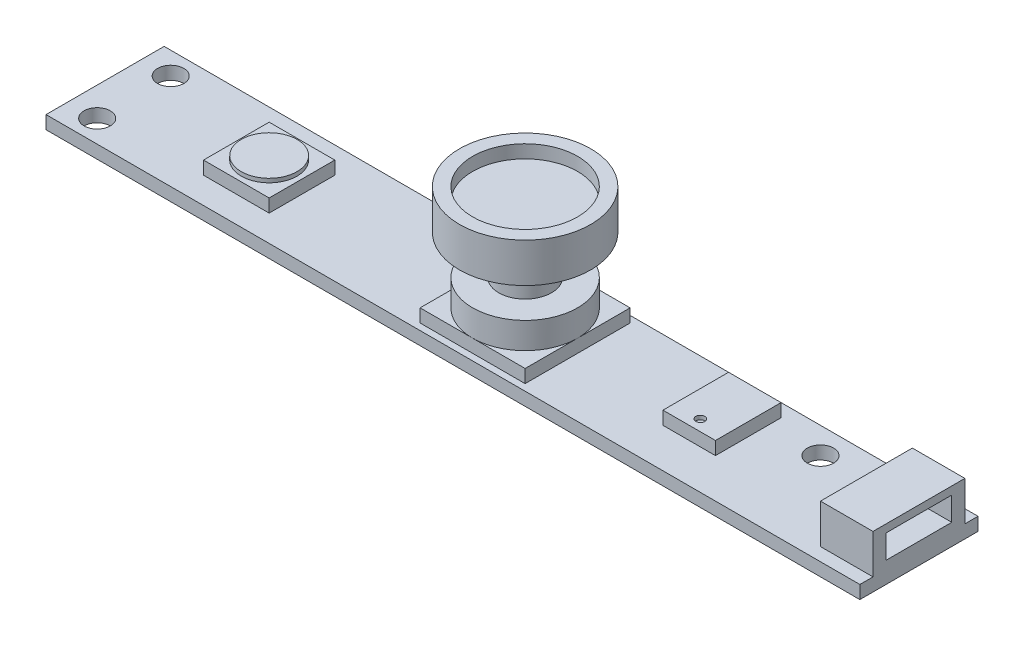
SolidWorks part; units mm, degrees
ref_plane "Front Plane" through (0, 0, 0) normal (0, 0, 1) x (1, 0, 0)
ref_plane "Top Plane" through (0, 0, 0) normal (0, 1, 0) x (1, 0, 0)
ref_plane "Right Plane" through (0, 0, 0) normal (1, 0, 0) x (0, 0, -1)
sketch "Sketch1" plane through (0, 0, 0) normal (0, 1, 0) x (1, 0, 0)
  line L1 (0, 0) -> (62, 0)
  line L2 (0, 0) -> (0, 9)
  line L3 (0, 9) -> (62, 9)
  line L4 (62, 0) -> (62, 9)
  dimension "D1" = 9
  dimension "D2" = 62
extrude "Boss-Extrude1" add sketch "Sketch1" along normal blind 1
sketch "Sketch2" plane through (0, 1, 0) normal (0, 1, 0) x (1, 0, 0)
  line L0 (62, 4.5) -> (0, 4.5) construction
  line L1 (62, 0) -> (62, 9) construction
  line L2 (0, 9) -> (0, 0) construction
  line L3 (31, 9) -> (31, 0) construction
  line L4 (62, 9) -> (0, 9) construction
  line L5 (0, 0) -> (62, 0) construction
  line L6 (62, 4.5) -> (62, 8)
  line L7 (62, 4.5) -> (62, 1)
  line L8 (62, 8) -> (58, 8)
  line L9 (58, 8) -> (58, 1)
  line L10 (58, 1) -> (62, 1)
  dimension "D1" = 3.5
  dimension "D2" = 3.5
  dimension "D3" = 4
extrude "Boss-Extrude2" add sketch "Sketch2" along normal blind 3
sketch "Sketch3" plane through (62, 0, 0) normal (1, 0, 0) x (0, 0, -1)
  line L11 (2, 3.4) -> (7, 3.4)
  line L12 (2, 3.4) -> (2, 1.6)
  line L13 (2, 1.6) -> (7, 1.6)
  line L14 (7, 3.4) -> (7, 1.6)
extrude "Cut-Extrude1" cut sketch "Sketch3" against normal blind 3
sketch "Sketch4" plane through (0, 1, 0) normal (0, 1, 0) x (1, 0, 0)
  line L0 (0, 4.5) -> (62, 4.5) construction
  line L1 (0, 9) -> (0, 0) construction
  line L2 (62, 1) -> (62, 8) construction
  line L4 (62, 9) -> (0, 9) construction
  line L5 (2.2, 9) -> (2.2, 0) construction
  line L6 (0, 0) -> (62, 0) construction
  circle A0 centre (2.2, 7.3) radius 1
  circle A1 centre (2.2, 1.7) radius 1
  circle A2 centre (52, 7) radius 1
extrude "Cut-Extrude2" cut sketch "Sketch4" against normal through all
sketch "Sketch5" plane through (0, 1, 0) normal (0, 1, 0) x (1, 0, 0)
  line L0 (62, 9) -> (62, 8)
  line L1 (62, 1) -> (62, 8) construction
  line L2 (62, 8) -> (31.4894, 8) construction
  line L3 (62, 9) -> (48, 9)
  line L4 (62, 9) -> (0, 9) construction
  line L5 (48, 9) -> (48, 0) construction
  line L6 (0, 0) -> (62, 0) construction
  line L8 (44, 9) -> (44, 0) construction
  line L9 (48, 8) -> (44, 8)
  line L10 (62, 3) -> (38.3098, 3) construction
  line L11 (48, 8) -> (48, 3)
  line L12 (48, 3) -> (44, 3)
  line L13 (44, 8) -> (44, 3)
  dimension "D1" = 1
  dimension "D2" = 14
extrude "Boss-Extrude4" add sketch "Sketch5" along normal blind 1 contours L9 L13 L12 L11 region at (46, 1, -5.5)
sketch "Sketch6" plane through (0, 1, 0) normal (0, 1, 0) x (1, 0, 0)
  line L0 (0, 9) -> (10, 9)
  line L1 (62, 9) -> (0, 9) construction
  line L2 (10, 9) -> (10, 0) construction
  line L3 (0, 0) -> (62, 0) construction
  line L4 (0, 4.5) -> (24.0117, 4.5) construction
  line L5 (0, 9) -> (0, 0) construction
  line L6 (10, 4.5) -> (10, 7)
  line L7 (10, 7) -> (15, 7)
  line L8 (15, 7) -> (15, 4.5)
  line L9 (15, 4.5) -> (15, 2)
  line L10 (15, 2) -> (10, 2)
  line L11 (10, 2) -> (10, 4.5)
  dimension "D1" = 10
  dimension "D2" = 2.5
  dimension "D3" = 2.5
  dimension "D4" = 5
extrude "Boss-Extrude5" add sketch "Sketch6" along normal blind 1 contours L11 L10 L9 L8 L7 L6 region at (12.5, 1, -4.5)
sketch "Sketch7" plane through (0, 2, 0) normal (0, 1, 0) x (1, 0, 0)
  line L0 (12.5, 7) -> (12.5, 2) construction
  line L1 (10, 7) -> (15, 7) construction
  line L2 (15, 2) -> (10, 2) construction
  line L3 (10, 4.5) -> (15, 4.5) construction
  line L4 (10, 2) -> (10, 7) construction
  line L5 (15, 7) -> (15, 2) construction
  circle A0 centre (12.5, 4.5) radius 2.126
extrude "Boss-Extrude6" add sketch "Sketch7" along normal blind 0.3
sketch "Sketch8" plane through (0, 1, 0) normal (0, 1, 0) x (1, 0, 0)
  line L0 (0, 4.5) -> (62, 4.5) construction
  line L1 (0, 9) -> (0, 0) construction
  line L2 (62, 1) -> (62, 8) construction
  line L3 (62, 9) -> (36, 9)
  line L4 (62, 9) -> (0, 9) construction
  line L5 (36, 9) -> (36, 0) construction
  line L6 (0, 0) -> (62, 0) construction
  line L7 (36, 9) -> (28, 9)
  line L8 (28, 9) -> (28, 0) construction
  line L9 (28, 4.5) -> (28, 0.5)
  line L10 (28, 0.5) -> (36, 0.5)
  line L11 (36, 0.5) -> (36, 4.5)
  line L12 (36, 4.5) -> (36, 8.5)
  line L13 (36, 8.5) -> (28, 8.5)
  line L14 (28, 8.5) -> (28, 4.5)
  dimension "D1" = 26
  dimension "D2" = 8
  dimension "D3" = 4
  dimension "D4" = 4
extrude "Boss-Extrude7" add sketch "Sketch8" along normal blind 1 contours L13 L14 L9 L10 L11 L12 region at (32, 1, -4.5)
sketch "Sketch9" plane through (0, 2, 0) normal (0, 1, 0) x (1, 0, 0)
  line L0 (28, 4.5) -> (36, 4.5) construction
  line L1 (28, 8.5) -> (28, 0.5) construction
  line L2 (36, 0.5) -> (36, 8.5) construction
  line L3 (32, 8.5) -> (32, 0.5) construction
  line L4 (36, 8.5) -> (28, 8.5) construction
  line L5 (28, 0.5) -> (36, 0.5) construction
  circle A0 centre (32, 4.5) radius 4
extrude "Boss-Extrude8" add sketch "Sketch9" along normal blind 2
sketch "Sketch10" plane through (0, 4, 0) normal (0, 1, 0) x (1, 0, 0)
  line L0 (32, 8.5) -> (32, 0.5) construction
  line L1 (28, 4.5) -> (36, 4.5) construction
  circle A0 centre (32, 4.5) radius 4 construction
  circle A1 centre (32, 4.5) radius 2.0145
extrude "Boss-Extrude9" add sketch "Sketch10" along normal blind 3
sketch "Sketch11" plane through (0, 7, 0) normal (0, 1, 0) x (1, 0, 0)
  line L0 (29.9855, 4.5) -> (34.0145, 4.5) construction
  line L1 (32, 6.5145) -> (32, 2.4855) construction
  circle A0 centre (32, 4.5) radius 2.0145 construction
  circle A1 centre (32, 4.5) radius 2.0145 construction
  circle A2 centre (32, 4.5) radius 5
extrude "Boss-Extrude10" add sketch "Sketch11" along normal blind 3
sketch "Sketch12" plane through (0, 10, 0) normal (0, 1, 0) x (1, 0, 0)
  line L0 (32, 9.5) -> (32, -0.5) construction
  circle A0 centre (32, 4.5) radius 5 construction
  circle A1 centre (32, 4.5) radius 4
extrude "Cut-Extrude3" cut sketch "Sketch12" against normal blind 1
sketch "Sketch13" plane through (0, 2, 0) normal (0, 1, 0) x (1, 0, 0)
  line L0 (46, 8) -> (46, 3) construction
  line L1 (48, 8) -> (44, 8) construction
  line L2 (48, 3) -> (44, 3) construction
  circle A0 centre (46, 3.8455) radius 0.3411
extrude "Cut-Extrude4" cut sketch "Sketch13" against normal blind 0.3
sketch "Sketch14" plane through (0, 0, 0) normal (0, -1, 0) x (1, 0, 0)
  line L0 (0, -4.5) -> (62, -4.5) construction
  line L1 (0, -9) -> (0, 0) construction
  line L2 (62, 0) -> (62, -9) construction
